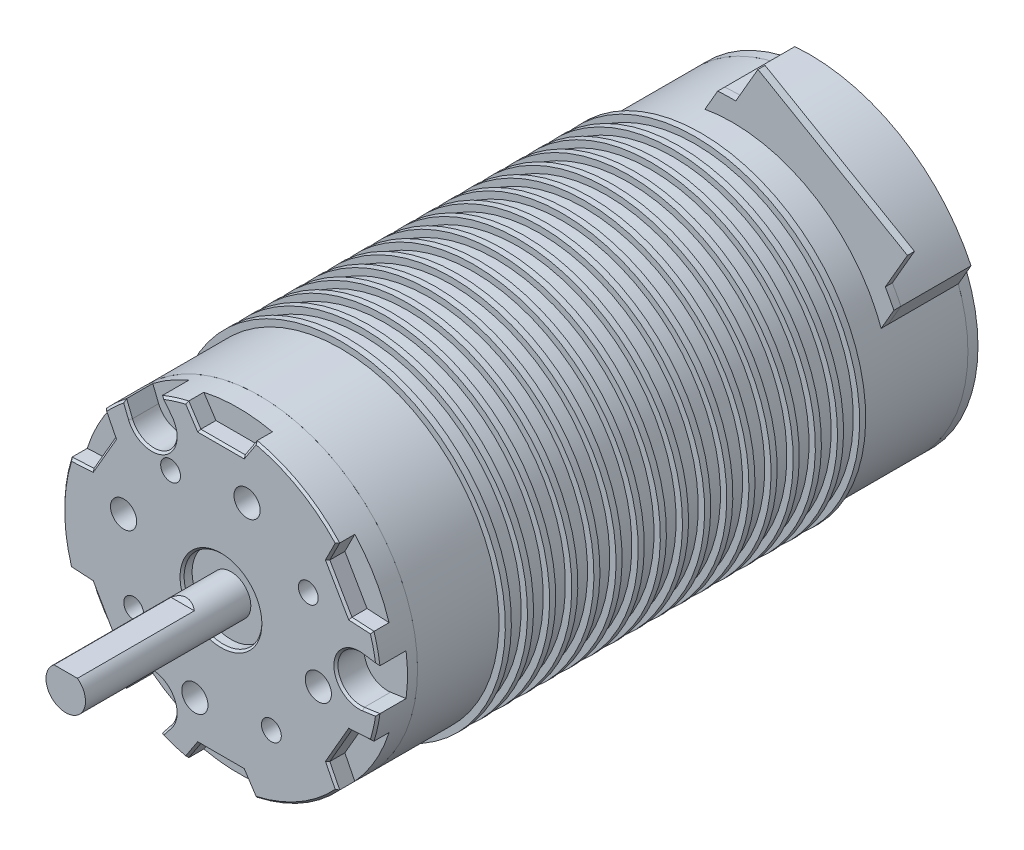
SolidWorks part; units mm, degrees
ref_plane "Front Plane" through (0, 0, 0) normal (0, 0, 1) x (1, 0, 0)
ref_plane "Top Plane" through (0, 0, 0) normal (0, 1, 0) x (1, 0, 0)
ref_plane "Right Plane" through (0, 0, 0) normal (1, 0, 0) x (0, 0, -1)
sketch "Sketch1" plane through (0, 0, 0) normal (0, 0, 1) x (1, 0, 0)
  circle A0 centre (0, 0) radius 19.939
  dimension "D1" = 39.878
extrude "Boss-Extrude1" add sketch "Sketch1" along normal blind 69.342
sketch "Sketch2" plane through (0, 0, 0) normal (0, 0, -1) x (-1, 0, 0)
  circle A0 centre (0, 0) radius 19.939
extrude "Boss-Extrude2" add sketch "Sketch2" along normal blind 1.27 separate body
sketch "Sketch4" plane through (0, 0, 69.342) normal (0, 0, 1) x (1, 0, 0)
  circle A0 centre (0, 0) radius 19.939
extrude "Boss-Extrude3" add sketch "Sketch4" along normal blind 4.826 separate body
sketch "Sketch5" plane through (0, 0, 74.168) normal (0, 0, 1) x (1, 0, 0)
  line L0 (0, 0) -> (0, 19.939) construction
  line L1 (-4.318, 19.4658) -> (-2.794, 17.145)
  line L2 (-2.794, 17.145) -> (2.794, 17.145)
  line L3 (2.794, 17.145) -> (4.318, 19.4658)
  circle A0 centre (0, 0) radius 19.939 construction
  arc A1 (-4.318, 19.4658) -> (4.318, 19.4658) centre (0, 0) cw
  point P3 (0, 17.145)
  dimension "D1" = 5.588
  dimension "D2" = 8.636
  dimension "D3" = 2.794
extrude "Cut-Extrude1" cut sketch "Sketch5" against normal blind 2.159 contours L1 L2 L3 A1
pattern_circular "CirPattern1" count 6 over 360 about axis through (0, 0, 0) along (0, 0, 1) of "Cut-Extrude1"
sketch "Sketch6" plane through (0, 0, 74.168) normal (0, 0, 1) x (1, 0, 0)
  line L0 (-4.318, 19.4658) -> (-7.62, 18.4255) construction
  line L1 (-14.6989, 13.4724) -> (-12.147, 15.8119) construction
  line L2 (-12.147, 15.8119) -> (-11.4096, 13.9782)
  line L3 (-7.62, 18.4255) -> (-6.4007, 16.8701)
  line L4 (-9.9695, 17.2677) -> (9.9695, -17.2677) construction
  arc A0 (-4.318, 19.4658) -> (-14.6989, 13.4724) centre (0, 0) ccw construction
  arc A1 (-11.4096, 13.9782) -> (-6.4007, 16.8701) centre (-8.6995, 15.068) ccw
  arc A3 (4.318, -19.4658) -> (14.6989, -13.4724) centre (0, 0) ccw construction
  arc A4 (-12.147, 15.8119) -> (-7.62, 18.4255) centre (0, 0) cw
  point P0 (-4.318, 19.4658)
  point P1 (-7.62, 18.4255)
  point P7 (-14.6989, 13.4724)
  point P8 (-12.147, 15.8119)
  dimension "D2" = 2.921
  dimension "D1" = 3.302
  dimension "D3" = 37.338
extrude "Cut-Extrude2" cut sketch "Sketch6" against normal blind 3.556 contours A1 L3 A4 L2
pattern_circular "CirPattern2" count 3 over 360 about axis through (0, 0, 0) along (0, 0, 1) of "Cut-Extrude2"
sketch "Sketch7" plane through (0, 0, 0) normal (1, 0, 0) x (0, 0, -1)
  line L0 (0, 19.939) -> (-69.342, 19.939) construction
  line L1 (-59.0804, 19.939) -> (-58.3184, 19.939)
  line L2 (-59.0804, 19.939) -> (-59.0804, 20.7391)
  line L3 (-59.0804, 20.7391) -> (-58.3184, 20.7391)
  line L4 (-58.3184, 19.939) -> (-58.3184, 20.7391)
  line L5 (-56.2904, 19.939) -> (-56.2904, 20.7391)
  line L6 (-56.2904, 19.939) -> (-55.5284, 19.939)
  line L7 (-55.5284, 19.939) -> (-55.5284, 20.7391)
  line L8 (-56.2904, 20.7391) -> (-55.5284, 20.7391)
  line L9 (-53.5003, 19.939) -> (-53.5003, 20.7391)
  line L10 (-53.5003, 19.939) -> (-52.7383, 19.939)
  line L11 (-52.7383, 19.939) -> (-52.7383, 20.7391)
  line L12 (-53.5003, 20.7391) -> (-52.7383, 20.7391)
  line L13 (-50.7103, 19.939) -> (-50.7103, 20.7391)
  line L14 (-50.7103, 19.939) -> (-49.9483, 19.939)
  line L15 (-49.9483, 19.939) -> (-49.9483, 20.7391)
  line L16 (-50.7103, 20.7391) -> (-49.9483, 20.7391)
  line L17 (-47.9203, 19.939) -> (-47.9203, 20.7391)
  line L18 (-47.9203, 19.939) -> (-47.1583, 19.939)
  line L19 (-47.1583, 19.939) -> (-47.1583, 20.7391)
  line L20 (-47.9203, 20.7391) -> (-47.1583, 20.7391)
  line L21 (-45.1302, 19.939) -> (-45.1302, 20.7391)
  line L22 (-45.1302, 19.939) -> (-44.3682, 19.939)
  line L23 (-44.3682, 19.939) -> (-44.3682, 20.7391)
  line L24 (-45.1302, 20.7391) -> (-44.3682, 20.7391)
  line L25 (-42.3402, 19.939) -> (-42.3402, 20.7391)
  line L26 (-42.3402, 19.939) -> (-41.5782, 19.939)
  line L27 (-41.5782, 19.939) -> (-41.5782, 20.7391)
  line L28 (-42.3402, 20.7391) -> (-41.5782, 20.7391)
  line L29 (-39.5502, 19.939) -> (-39.5502, 20.7391)
  line L30 (-39.5502, 19.939) -> (-38.7882, 19.939)
  line L31 (-38.7882, 19.939) -> (-38.7882, 20.7391)
  line L32 (-39.5502, 20.7391) -> (-38.7882, 20.7391)
  line L33 (-36.7601, 19.939) -> (-36.7601, 20.7391)
  line L34 (-36.7601, 19.939) -> (-35.9982, 19.939)
  line L35 (-35.9982, 19.939) -> (-35.9982, 20.7391)
  line L36 (-36.7601, 20.7391) -> (-35.9982, 20.7391)
  line L37 (-33.9701, 19.939) -> (-33.9701, 20.7391)
  line L38 (-33.9701, 19.939) -> (-33.2081, 19.939)
  line L39 (-33.2081, 19.939) -> (-33.2081, 20.7391)
  line L40 (-33.9701, 20.7391) -> (-33.2081, 20.7391)
  line L41 (-31.1801, 19.939) -> (-31.1801, 20.7391)
  line L42 (-31.1801, 19.939) -> (-30.4181, 19.939)
  line L43 (-30.4181, 19.939) -> (-30.4181, 20.7391)
  line L44 (-31.1801, 20.7391) -> (-30.4181, 20.7391)
  line L45 (-28.3901, 19.939) -> (-28.3901, 20.7391)
  line L46 (-28.3901, 19.939) -> (-27.6281, 19.939)
  line L47 (-27.6281, 19.939) -> (-27.6281, 20.7391)
  line L48 (-28.3901, 20.7391) -> (-27.6281, 20.7391)
  line L49 (-25.6, 19.939) -> (-25.6, 20.7391)
  line L50 (-25.6, 19.939) -> (-24.838, 19.939)
  line L51 (-24.838, 19.939) -> (-24.838, 20.7391)
  line L52 (-25.6, 20.7391) -> (-24.838, 20.7391)
  line L53 (-22.81, 19.939) -> (-22.81, 20.7391)
  line L54 (-22.81, 19.939) -> (-22.048, 19.939)
  line L55 (-22.048, 19.939) -> (-22.048, 20.7391)
  line L56 (-22.81, 20.7391) -> (-22.048, 20.7391)
  line L57 (-20.02, 19.939) -> (-20.02, 20.7391)
  line L58 (-20.02, 19.939) -> (-19.258, 19.939)
  line L59 (-19.258, 19.939) -> (-19.258, 20.7391)
  line L60 (-20.02, 20.7391) -> (-19.258, 20.7391)
  line L61 (-17.2299, 19.939) -> (-17.2299, 20.7391)
  line L62 (-17.2299, 19.939) -> (-16.4679, 19.939)
  line L63 (-16.4679, 19.939) -> (-16.4679, 20.7391)
  line L64 (-17.2299, 20.7391) -> (-16.4679, 20.7391)
  line L65 (-14.4399, 19.939) -> (-14.4399, 20.7391)
  line L66 (-14.4399, 19.939) -> (-13.6779, 19.939)
  line L67 (-13.6779, 19.939) -> (-13.6779, 20.7391)
  line L68 (-14.4399, 20.7391) -> (-13.6779, 20.7391)
  line L69 (1.27, 0) -> (-74.168, 0) construction
  line L70 (1.27, -19.939) -> (1.27, 19.939) construction
  line L71 (-74.168, 2.921) -> (-74.168, -2.921) construction
  dimension "D1" = 0.8001
  dimension "D2" = 0.762
  dimension "D3" = 15.0876
  dimension "D5" = 14.9479
  dimension "D4" = 17
revolve "Revolve1" add sketch "Sketch7" angle 360 about L69
sketch "Sketch8" plane through (0, 0, 74.168) normal (0, 0, 1) x (1, 0, 0)
  circle A0 centre (0, 0) radius 4.9022
  dimension "D1" = 9.8044
extrude "Cut-Extrude3" cut sketch "Sketch8" against normal blind 1.27
sketch "Sketch9" plane through (0, 0, 72.898) normal (0, 0, 1) x (1, 0, 0)
  circle A0 centre (0, 0) radius 2.4892
  dimension "D1" = 4.9784
extrude "Boss-Extrude4" add sketch "Sketch9" along normal blind 20.828
sketch "Sketch10" plane through (0, 0, 93.726) normal (0, 0, 1) x (1, 0, 0)
  line L0 (-1.473, 2.0066) -> (1.473, 2.0066)
  line L1 (0, 2.4892) -> (0, -2.4892) construction
  circle A0 centre (0, 0) radius 2.4892 construction
  circle A1 centre (0, 0) radius 2.4892 construction
  arc A2 (-1.473, 2.0066) -> (1.473, 2.0066) centre (0, 0) cw
  point P11 (0, 2.0066)
  dimension "D1" = 4.4958
extrude "Cut-Extrude4" cut sketch "Sketch10" against normal blind 15.24
chamfer "Chamfer2" distance 0.508 angle 46 1 edges at (0, 2.0066, 78.486)
chamfer "Chamfer3" distance 0.254 angle 46 37 edges at (-7.239, -12.5383, 74.168) (-11.7783, -14.895, 74.168) (-13.4738, -14.6976, 74.168) (-14.075, -12.2323, 74.168) (-14.848, -8.5725, 74.168) (-17.631, -6.0731, 74.168) (-19.939, 0, 74.168) (-17.631, 6.0731, 74.168) (-14.848, 8.5725, 74.168) (-14.075, 12.2323, 74.168) (-13.4738, 14.6976, 74.168) (-11.7783, 14.895, 74.168) (-7.239, 12.5383, 74.168) (-7.0103, 17.6478, 74.168) (-5.9916, 19.0175, 74.168) (-3.556, 18.3054, 74.168) (0, 17.145, 74.168) (3.556, 18.3054, 74.168) (9.9695, 17.2677, 74.168) (14.075, 12.2323, 74.168) (14.848, 8.5725, 74.168) (17.631, 6.0731, 74.168) (19.4654, 4.3198, 74.168) (18.7886, 2.7528, 74.168) (14.478, 0, 74.168) (18.7886, -2.7528, 74.168) (19.4654, -4.3198, 74.168) (17.631, -6.0731, 74.168) (14.848, -8.5725, 74.168) (14.075, -12.2323, 74.168) (9.9695, -17.2677, 74.168) (3.556, -18.3054, 74.168) (0, -17.145, 74.168) (-3.556, -18.3054, 74.168) (-5.9916, -19.0175, 74.168) (-7.0103, -17.6478, 74.168) (4.9022, 0, 74.168)
sketch "Sketch11" plane through (0, 0, -1.27) normal (0, 0, -1) x (-1, 0, 0)
  line L0 (0, 0) -> (0, 19.939) construction
  line L1 (0, 0) -> (-9.9695, 17.2677) construction
  circle A0 centre (0, 0) radius 19.939 construction
  dimension "D1" = 30
ref_plane "Plane1" through (0, 0, 0) normal (0.866, -0.5, 0) x (0, 0, -1)
sketch "Sketch12" plane through (0, 0, 0) normal (0.866, -0.5, 0) x (0, 0, -1)
  line L0 (0, 0) -> (-72.009, 0) construction
  line L1 (0, 19.939) -> (-8.8392, 19.939)
  line L2 (0, 19.939) -> (0, 22.479)
  line L3 (0, 22.479) -> (-8.8392, 22.479)
  line L4 (-8.8392, 19.939) -> (-8.8392, 22.479)
  line L9 (-72.009, 4.318) -> (-72.009, -4.318) construction
  dimension "D1" = 8.8392
  dimension "D2" = 2.54
revolve "Revolve2" add sketch "Sketch12" angle 40 about L0
sketch "Sketch13" plane through (0, 0, 0) normal (0, 0, -1) x (-1, 0, 0)
  line L0 (-18.7365, 6.8195) -> (-20.3331, 9.5849)
  line L1 (-8.8713, 15.3655) -> (8.8713, -15.3655) construction
  line L2 (3.4624, 19.6361) -> (1.8658, 22.4014)
  line L3 (-21.1234, 7.6883) -> (-18.7365, 6.8195)
  line L4 (3.9034, 22.1375) -> (3.4624, 19.6361)
  arc A0 (3.9034, 22.1375) -> (-21.1234, 7.6883) centre (0, 0) ccw construction
  arc A1 (-21.1234, 7.6883) -> (-20.3331, 9.5849) centre (0, 0) cw
  arc A2 (1.8658, 22.4014) -> (3.9034, 22.1375) centre (0, 0) cw
extrude "Cut-Extrude5" cut sketch "Sketch13" against normal up to next (8.8392 mm away)
sketch "Sketch14" plane through (0, 0, 8.8392) normal (0, 0, 1) x (1, 0, 0)
  line L0 (-3.4624, 19.6361) -> (-1.8658, 22.4014)
  line L1 (0.4202, 22.4751) -> (3.2142, 27.3144)
  line L2 (-8.8713, -15.3655) -> (8.8713, 15.3655) construction
  line L3 (3.2142, 27.3144) -> (22.0479, 16.4408)
  line L4 (18.7365, 6.8195) -> (20.3331, 9.5849)
  line L5 (19.2539, 11.6014) -> (22.0479, 16.4408)
  arc A0 (-1.8658, 22.4014) -> (0.4202, 22.4751) centre (0, 0) cw
  arc A1 (20.3331, 9.5849) -> (-1.8658, 22.4014) centre (0, 0) ccw construction
  arc A2 (-3.4624, 19.6361) -> (18.7365, 6.8195) centre (0, 0) cw
  arc A3 (18.7365, 6.8195) -> (-3.4624, 19.6361) centre (0, 0) ccw construction
  arc A4 (20.3331, 9.5849) -> (19.2539, 11.6014) centre (0, 0) ccw
  point P22 (12.631, 21.8776)
  dimension "D1" = 5.588
  dimension "D2" = 2.286
extrude "Boss-Extrude5" add sketch "Sketch14" along normal blind 0.889 separate body
sketch "Sketch15" plane through (0, 0, 74.168) normal (0, 0, 1) x (1, 0, 0)
  line L0 (-9.9695, 17.2677) -> (0, 0) construction
  arc A0 (-7.62, 18.4255) -> (-12.147, 15.8119) centre (0, 0) ccw construction
  circle A1 centre (0, 0) radius 12.7 construction
  point P7 (-6.35, 10.9985)
  point P8 (3.287, 12.2673)
  point P11 (10.9985, 6.35)
  point P12 (12.2673, -3.287)
  point P13 (6.35, -10.9985)
  point P14 (-3.287, -12.2673)
  point P15 (-10.9985, -6.35)
  point P16 (-12.2673, 3.287)
  point P17 (0, 0)
  dimension "D1" = 25.4
  dimension "D2" = 8
hole_wizard "M3x0.5 Tapped Hole1" positions "Sketch16" profile "Sketch17" tap size "M3x0.5" standard "ANSI Metric"
sketch "Sketch16" plane through (0, 0, 74.168) normal (0, 0, 1) x (1, 0, 0)
  point P0 (-6.35, 10.9985)
  point P3 (10.9985, 6.35)
  point P6 (6.35, -10.9985)
  point P9 (-10.9985, -6.35)
sketch "Sketch17" plane through (-6.35, 10.9985, 74.168) normal (1, 0, 0) x (0, -1, 0)
  line L0 (0, 0) -> (0, 7.62)
  line L1 (0, 7.62) -> (1.25, 6.8689)
  line L2 (1.25, 6.8689) -> (1.25, 0)
  line L5 (1.25, 0) -> (0, 0)
  line L10 (0, 7.62) -> (-1.25, 6.8689) construction
  line L11 (0, -6.35) -> (0, 107.95) construction
  dimension "Tap Drill Dia." = 2.5
  dimension "Tap Drill Depth" = 7.62
  dimension "Drill Angle" = 118
hole_wizard "M4x0.7 Tapped Hole1" positions "Sketch18" profile "Sketch19" tap size "M4x0.7" standard "ANSI Metric"
sketch "Sketch18" plane through (0, 0, 74.168) normal (0, 0, 1) x (1, 0, 0)
  point P0 (3.287, 12.2673)
  point P3 (12.2673, -3.287)
  point P6 (-3.287, -12.2673)
  point P9 (-12.2673, 3.287)
sketch "Sketch19" plane through (3.287, 12.2673, 74.168) normal (1, 0, 0) x (0, -1, 0)
  line L0 (0, 0) -> (0, 9.906)
  line L1 (0, 9.906) -> (1.65, 8.9146)
  line L2 (1.65, 8.9146) -> (1.65, 0)
  line L5 (1.65, 0) -> (0, 0)
  line L10 (0, 9.906) -> (-1.65, 8.9146) construction
  line L11 (0, -6.35) -> (0, 107.95) construction
  dimension "Tap Drill Dia." = 3.3
  dimension "Tap Drill Depth" = 9.906
  dimension "Drill Angle" = 118
